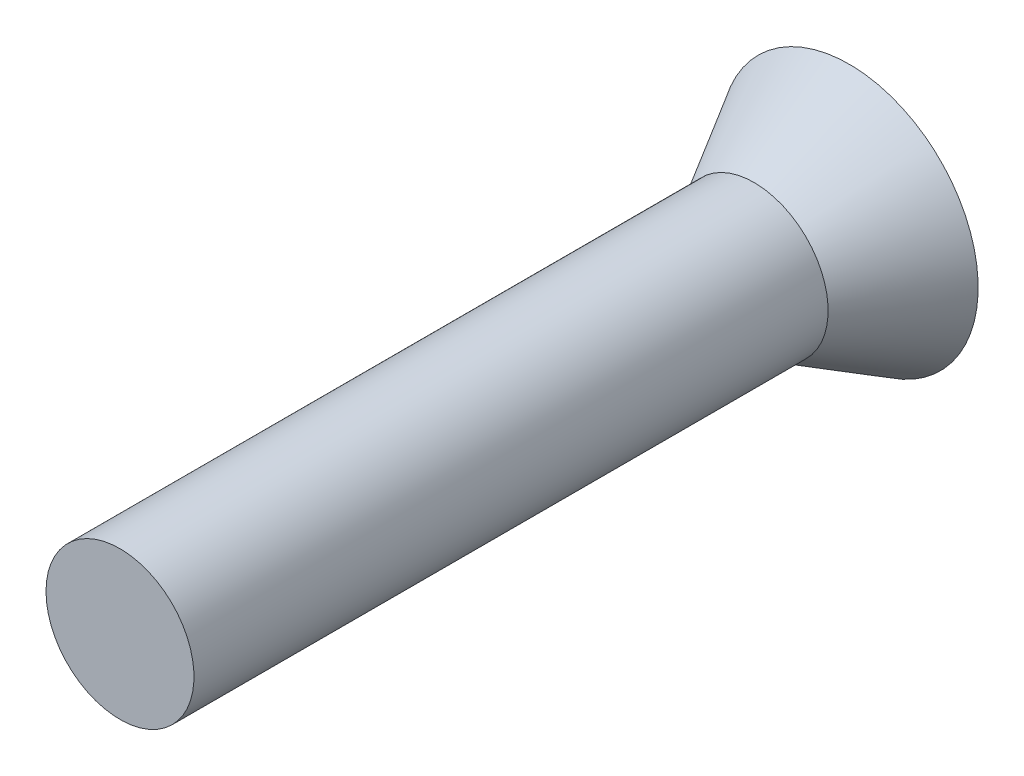
SolidWorks part; units mm, degrees
ref_plane "Front Plane" through (0, 0, 0) normal (0, 0, 1) x (1, 0, 0)
ref_plane "Top Plane" through (0, 0, 0) normal (0, 1, 0) x (1, 0, 0)
ref_plane "Right Plane" through (0, 0, 0) normal (1, 0, 0) x (0, 0, -1)
sketch "Sketch2" plane through (0, 0, 0) normal (0, 1, 0) x (1, 0, 0)
  line L0 (0, 52.4496) -> (0, -53.3311) construction
  line L1 (0, 0) -> (0, 5.9)
  line L2 (0, 5.9) -> (-1.2196, 5.9)
  line L3 (-1.2196, 5.9) -> (-0.7, 5)
  line L4 (-0.7, 5) -> (-0.7, -1)
  line L5 (-0.7, -1) -> (0, -1)
  line L6 (0, -1) -> (0, 0)
  dimension "D1" = 30
  dimension "D2" = 0.9
  dimension "D3" = 6
  dimension "D4" = 0.7
  dimension "D5" = 1
revolve "Revolve1" add sketch "Sketch2" angle 360 about L0
sketch "Sketch4" plane through (0, 0, -5.9) normal (0, 0, -1) x (-1, 0, 0)
  line L0 (0, 0) -> (0, 0.8954) construction
  line L1 (0, 0.75) -> (-0.1968, 0.75)
  line L2 (-0.1968, 0.75) -> (-0.1968, 0.1968)
  line L3 (-0.1968, 0.1968) -> (-0.75, 0.1968)
  line L4 (-0.75, 0.1968) -> (-0.75, -0.1968)
  line L5 (-0.75, -0.1968) -> (-0.1968, -0.1968)
  line L6 (-0.1968, -0.1968) -> (-0.1968, -0.75)
  line L7 (-0.1968, -0.75) -> (0.1968, -0.75)
  line L8 (0.1968, -0.75) -> (0.1968, -0.1968)
  line L9 (0.1968, -0.1968) -> (0.75, -0.1968)
  line L10 (0.75, -0.1968) -> (0.75, 0.1968)
  line L11 (0.75, 0.1968) -> (0.1968, 0.1968)
  line L12 (0.1968, 0.1968) -> (0.1968, 0.75)
  line L13 (0.1968, 0.75) -> (0, 0.75)
  line L14 (0, 0) -> (-0.75, 0) construction
  dimension "D1" = 1.5
extrude "Cut-Extrude1" cut sketch "Sketch4" against normal blind 0.25
chamfer "Chamfer1" distance 0.1 angle 45 4 edges at (0.1968, -0.1968, -5.775) (-0.1968, -0.1968, -5.775) (-0.1968, 0.1968, -5.775) (0.1968, 0.1968, -5.775)
chamfer "Chamfer2" distance 0.1 angle 45 8 edges at (-0.75, 0.1968, -5.775) (-0.75, -0.1968, -5.775) (-0.1968, -0.75, -5.775) (0.1968, -0.75, -5.775) (0.75, -0.1968, -5.775) (0.75, 0.1968, -5.775) (0.1968, 0.75, -5.775) (-0.1968, 0.75, -5.775)
chamfer "Chamfer3" distance 0.25 angle 45 4 edges at (0, -0.75, -5.65) (0.75, 0, -5.65) (-0.75, 0, -5.65) (0, 0.75, -5.65)
